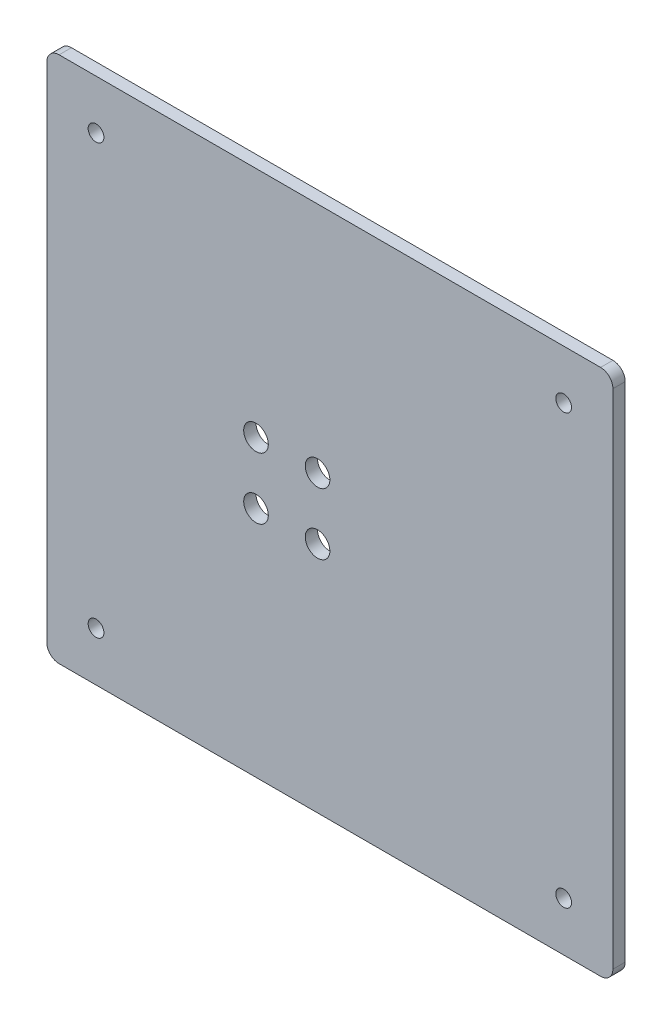
SolidWorks part; units mm, degrees
ref_plane "前视基准面" through (0, 0, 0) normal (0, 0, 1) x (1, 0, 0)
ref_plane "上视基准面" through (0, 0, 0) normal (0, 1, 0) x (1, 0, 0)
ref_plane "右视基准面" through (0, 0, 0) normal (1, 0, 0) x (0, 0, -1)
sketch "草图1" plane through (0, 0, 0) normal (0, 0, 1) x (1, 0, 0)
  line L1 (85, -77.125) -> (-85, -77.125)
  line L2 (85, -77.125) -> (85, 77.125)
  line L3 (85, 77.125) -> (-85, 77.125)
  line L4 (-85, -77.125) -> (-85, 77.125)
  line L5 (85, -77.125) -> (-85, 77.125) construction
  line L6 (85, 77.125) -> (-85, -77.125) construction
  line L7 (80, -72.125) -> (-80, -72.125)
  line L8 (80, -72.125) -> (80, 72.125)
  line L9 (80, 72.125) -> (-80, 72.125)
  line L10 (-80, -72.125) -> (-80, 72.125)
  line L11 (80, -72.125) -> (-80, 72.125) construction
  line L12 (80, 72.125) -> (-80, -72.125) construction
  point P0 (0, 0)
  point P6 (0, 0)
  dimension "D1" = 170
  dimension "D2" = 154.25
  dimension "D3" = 5
  dimension "D4" = 5
extrude "凸台-拉伸1" add sketch "草图1" along normal blind 8
fillet "圆角1" radius 5 8 edges at (-80, 72.125, 4) (80, 72.125, 4) (80, -72.125, 4) (-80, -72.125, 4) (85, -77.125, 4) (-85, -77.125, 4) (-85, 77.125, 4) (85, 77.125, 4)
sketch "草图2" plane through (0, 0, 8) normal (0, 0, 1) x (1, 0, 0)
  line L1 (115, -107.125) -> (-115, -107.125)
  line L2 (115, -107.125) -> (115, 107.125)
  line L3 (115, 107.125) -> (-115, 107.125)
  line L4 (-115, -107.125) -> (-115, 107.125)
  line L5 (115, -107.125) -> (-115, 107.125) construction
  line L6 (115, 107.125) -> (-115, -107.125) construction
  point P0 (0, 0)
  dimension "D1" = 214.25
  dimension "D2" = 230
extrude "凸台-拉伸2" add sketch "草图2" along normal blind 5
fillet "圆角2" radius 5 4 edges at (-115, 107.125, 10.5) (115, 107.125, 10.5) (115, -107.125, 10.5) (-115, -107.125, 10.5)
sketch "草图3" plane through (0, 0, 13) normal (0, 0, 1) x (1, 0, 0)
  line L4 (85, -72.125) -> (85, 72.125) construction
  line L5 (-85, 72.125) -> (-85, -72.125) construction
  line L6 (-85, 72.125) -> (-85, -72.125) construction
  line L7 (85, -72.125) -> (85, 72.125) construction
  line L8 (80, 77.125) -> (-80, 77.125) construction
  line L9 (-80, -77.125) -> (80, -77.125) construction
  point P0 (-95, 87.125)
  point P1 (-95, -87.125)
  point P2 (95, -87.125)
  point P3 (95, 87.125)
  dimension "D1" = 10
  dimension "D2" = 10
  dimension "D3" = 10
  dimension "D4" = 10
  dimension "D5" = 10
  dimension "D6" = 10
  dimension "D7" = 10
  dimension "D8" = 10
hole_wizard "Ø6.4 (6.4) 直径孔1" positions "草图4" profile "草图5" hole size "Ø6.4" standard "GB" end condition up to next
sketch "草图4" plane through (0, 0, 13) normal (0, 0, 1) x (1, 0, 0)
  point P0 (-95, 87.125)
  point P3 (95, 87.125)
  point P6 (95, -87.125)
  point P9 (-95, -87.125)
sketch "草图5" plane through (-95, 87.125, 13) normal (1, 0, 0) x (0, -1, 0)
  line L0 (0, 0) -> (0, 5)
  line L1 (0, 5) -> (3.2, 5)
  line L2 (3.2, 5) -> (3.2, 0)
  line L5 (3.2, 0) -> (0, 0)
  line L11 (0, -6.35) -> (0, 107.95) construction
  dimension "通孔孔直径" = 6.4
  dimension "通孔孔深度" = 5
sketch "草图7" plane through (0, 0, 13) normal (0, 0, 1) x (1, 0, 0)
  line L0 (115, -102.125) -> (115, 102.125) construction
  point P0 (-5, 12.5)
  point P1 (-30, 12.5)
  point P2 (-30, -12.5)
  point P3 (-5, -12.5)
  dimension "D1" = 25
  dimension "D2" = 25
  dimension "D3" = 25
  dimension "D4" = 25
  dimension "D5" = 120
  dimension "D6" = 12.5
hole_wizard "Ø10.0 (10) 直径孔1" positions "草图8" profile "草图9" hole size "Ø10.0" standard "GB" end condition through all
sketch "草图8" plane through (0, 0, 13) normal (0, 0, 1) x (1, 0, 0)
  point P0 (-30, 12.5)
  point P3 (-5, 12.5)
  point P6 (-5, -12.5)
  point P9 (-30, -12.5)
sketch "草图9" plane through (-30, 12.5, 13) normal (1, 0, 0) x (0, -1, 0)
  line L0 (0, 0) -> (0, 13)
  line L1 (0, 13) -> (5, 13)
  line L2 (5, 13) -> (5, 0)
  line L5 (5, 0) -> (0, 0)
  line L11 (0, -6.35) -> (0, 107.95) construction
  dimension "通孔孔直径" = 10
  dimension "通孔孔深度" = 13
